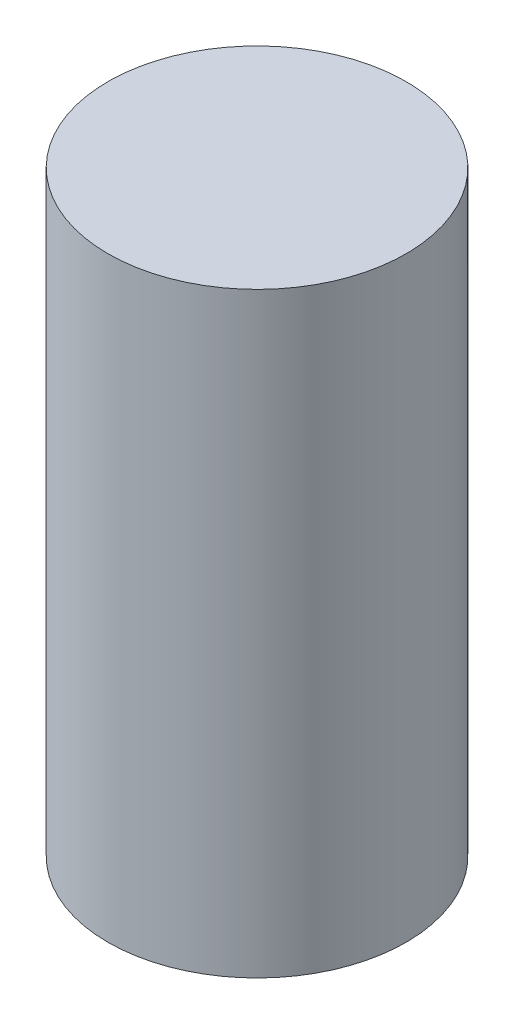
SolidWorks part; units mm, degrees
ref_plane "Front Plane" through (0, 0, 0) normal (0, 0, 1) x (1, 0, 0)
ref_plane "Top Plane" through (0, 0, 0) normal (0, 1, 0) x (1, 0, 0)
ref_plane "Right Plane" through (0, 0, 0) normal (1, 0, 0) x (0, 0, -1)
sketch "Sketch1" plane through (0, 0, 0) normal (0, 1, 0) x (1, 0, 0)
  circle A0 centre (0, 0) radius 25.4
  dimension "D1" = 50.8
extrude "Boss-Extrude1" add sketch "Sketch1" along normal blind 101.6
ref_axis "Axis1" through (0, -5.08, 0) along (0, 1, 0)
